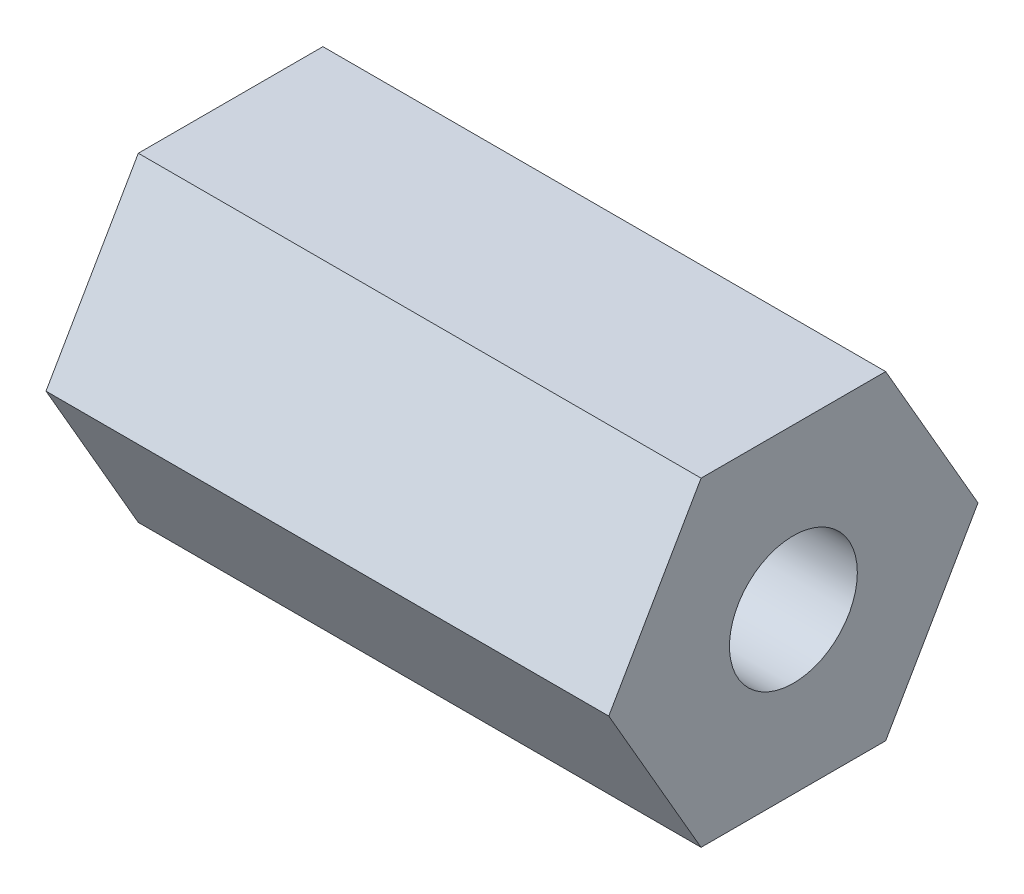
SolidWorks part; units mm, degrees
material "6061 Alloy"
ref_plane "Front" through (0, 0, 0) normal (0, 0, 1) x (1, 0, 0)
ref_plane "Top" through (0, 0, 0) normal (0, 1, 0) x (1, 0, 0)
ref_plane "Right" through (0, 0, 0) normal (1, 0, 0) x (0, 0, -1)
sketch "Sketch1" plane through (0, 0, 0) normal (1, 0, 0) x (0, 0, -1)
  line L1 (3.6662, 6.35) -> (-3.6662, 6.35)
  line L2 (-3.6662, 6.35) -> (-7.3323, 0)
  line L3 (-7.3323, 0) -> (-3.6662, -6.35)
  line L4 (-3.6662, -6.35) -> (3.6662, -6.35)
  line L5 (3.6662, -6.35) -> (7.3323, 0)
  line L6 (7.3323, 0) -> (3.6662, 6.35)
  circle A0 centre (0, 0) radius 6.35 construction
  dimension "D1" = 12.7
extrude "Boss-Extrude1" add sketch "Sketch1" along normal blind 22.352
sketch "Sketch2" [suppressed] plane through (92.075, 0, 0) normal (1, 0, 0) x (0, 0, -1)
  circle A0 centre (0, 0) radius 2.413
  dimension "D1" = 4.826
extrude "Cut-Extrude1" [suppressed] cut sketch "Sketch2" against normal blind 25.4
sketch "Sketch3" [suppressed] plane through (0, 3.175, 5.4993) normal (0, 0.5, 0.866) x (1, 0, 0)
  line L0 (0, 3.6662) -> (0, -3.6662) construction
  line L1 (0, 0) -> (47.0154, 0) construction
  circle A0 centre (47.0154, 0) radius 1.778
  dimension "D2" = 3.556
  dimension "D1" = 47.0154
extrude "Cut-Extrude2" [suppressed] cut sketch "Sketch3" against normal blind 25.4
sketch "Sketch4" plane through (22.352, 0, 0) normal (1, 0, 0) x (0, 0, -1)
  circle A0 centre (0, 0) radius 2.54
  dimension "D1" = 5.08
extrude "Cut-Extrude3" cut sketch "Sketch4" against normal through all
